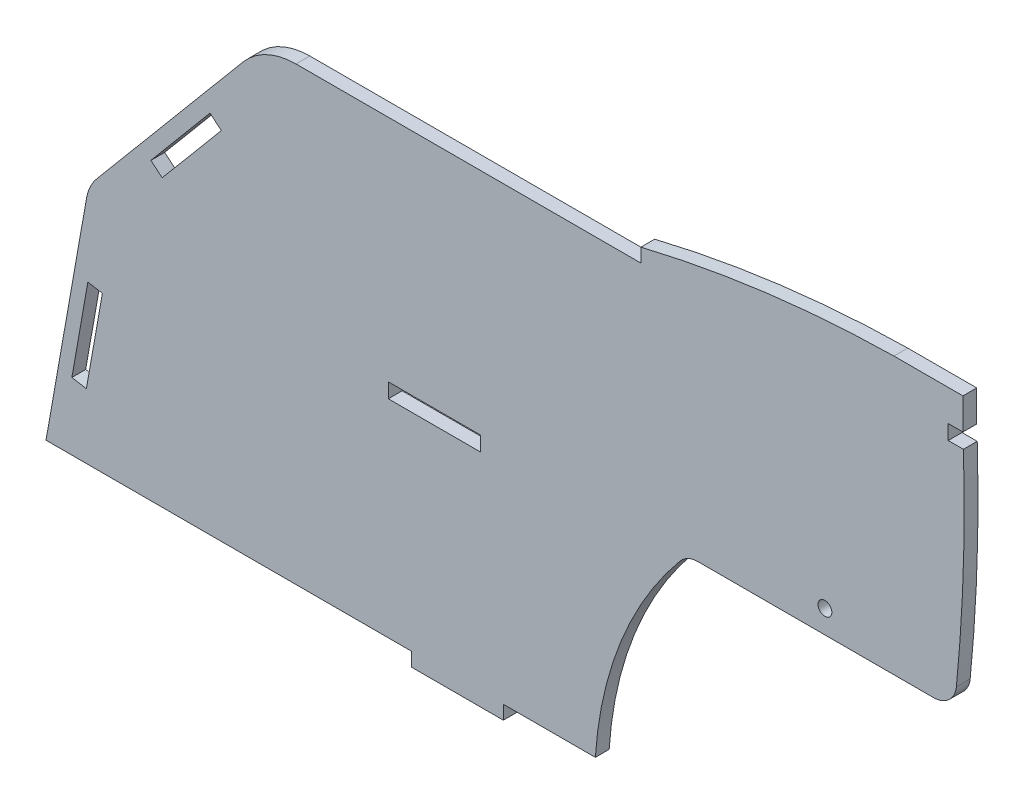
SolidWorks part; units mm, degrees
material "Acrylic (Medium-high impact)"
ref_plane "Front Plane" through (0, 0, 0) normal (0, 0, 1) x (1, 0, 0)
ref_plane "Top Plane" through (0, 0, 0) normal (0, 1, 0) x (1, 0, 0)
ref_plane "Right Plane" through (0, 0, 0) normal (1, 0, 0) x (0, 0, -1)
sketch "Sketch1" plane through (0, 0, 0) normal (0, 0, 1) x (1, 0, 0)
  line L0 (-45.0693, 73) -> (29.8996, 73)
  line L6 (93.5002, 23) -> (42.2917, 23)
  line L13 (-25, 23.2) -> (-5, 23.2)
  line L14 (-25, 23.2) -> (-25, 20)
  line L15 (-25, 20) -> (-5, 20)
  line L16 (-5, 23.2) -> (-5, 20)
  line L17 (-25, 23.2) -> (-5, 20) construction
  line L18 (-25, 20) -> (-5, 23.2) construction
  line L25 (-99.4082, -25) -> (-20, -25)
  line L26 (-20, -25) -> (-20, -27.9999)
  line L27 (-20, -27.9999) -> (0, -27.9999)
  line L28 (0, -27.9999) -> (0, -25)
  line L29 (0, -25) -> (20, -25)
  line L30 (0, 0) -> (-95, 0) construction
  line L31 (-88.4042, 29.6914) -> (-56.56, 67.6418)
  line L32 (-76.6118, 39.0778) -> (-74.1605, 37.0209)
  line L33 (-76.6118, 39.0778) -> (-63.7561, 54.3987)
  line L34 (-74.1605, 37.0209) -> (-61.3047, 52.3418)
  line L35 (-63.7561, 54.3987) -> (-61.3047, 52.3418)
  line L36 (-70.184, 46.7382) -> (-72.4821, 48.6666) construction
  line L38 (-90.5918, 25) -> (-99.4082, -25)
  line L39 (-93.7821, -10.369) -> (-90.3091, 9.3271)
  line L40 (-93.7821, -10.369) -> (-90.6307, -10.9247)
  line L41 (-90.3091, 9.3271) -> (-87.1577, 8.7715)
  line L42 (-90.6307, -10.9247) -> (-87.1577, 8.7715)
  line L43 (-92.0456, -0.5209) -> (-95, 0) construction
  line L44 (99.8996, 83) -> (84.8996, 83)
  line L45 (29.8996, 73) -> (29.8996, 76)
  line L46 (99.8996, 83) -> (99.8996, 76)
  arc A3 (20, -25) -> (38.4554, 21.2066) centre (99.8373, -30.0989) cw
  arc A5 (-45.0693, 73) -> (-56.56, 67.6418) centre (-45.0693, 58) ccw
  arc A7 (-88.4042, 29.6914) -> (-90.5918, 25) centre (-80.7437, 23.2635) ccw
  arc A13 (42.2917, 23) -> (38.4554, 21.2066) centre (42.2917, 18) ccw
  circle A14 centre (69.8996, 28) radius 1.5
  arc A17 (29.8996, 76) -> (84.8996, 83) centre (88.7685, -166.9701) cw
  arc A20 (98.4759, 27.5072) -> (99.8996, 76) centre (-249.8203, 62.0006) ccw
  arc A21 (98.4759, 27.5072) -> (93.5002, 23) centre (93.5002, 28) cw
  point P1 (0, 0)
  point P11 (-15, 21.6)
  point P33 (-95, 0)
  point P38 (-90.1265, 27.6388)
  point P45 (40, 23)
  point P52 (98, 23)
  dimension "D7" = 7
  dimension "D3" = 15
  dimension "D9" = 98
  dimension "D10" = 58
  dimension "D12" = 80
  dimension "D2" = 25
  dimension "D11" = 10
  dimension "D8" = 10
  dimension "D20" = 15
  dimension "D21" = 70
  dimension "D22" = 5
  dimension "D23" = 3
  dimension "D29" = 250
  dimension "D27" = 145
  dimension "D30" = 350
  dimension "D31" = 78
  dimension "D32" = 30
  dimension "D33" = 5
  dimension "D4" = 20
  dimension "D5" = 3.2
  dimension "D6" = 45
  dimension "D13" = 20
  dimension "D14" = 130
  dimension "D15" = 3
  dimension "D16" = 3
  dimension "100" = 95
  dimension "D17" = 280
  dimension "D18" = 15
  dimension "D19" = 20
  dimension "D24" = 48
  dimension "D25" = 2.9999
  dimension "D26" = 5
  dimension "D28" = 3
extrude "Boss-Extrude1" add sketch "Sketch1" along normal blind 3
sketch "Sketch2" plane through (0, 0, 3) normal (0, 0, 1) x (1, 0, 0)
  line L1 (96.7019, 76.2) -> (100.2019, 76.2)
  line L2 (96.7019, 76.2) -> (96.7019, 73)
  line L3 (96.7019, 73) -> (100.2019, 73)
  line L4 (100.2019, 76.2) -> (100.2019, 73)
  line L5 (96.7019, 76.2) -> (100.2019, 73) construction
  line L6 (96.7019, 73) -> (100.2019, 76.2) construction
  line L10 (29.8996, 73) -> (-45.0693, 73) construction
  arc A5 (98.4759, 27.5072) -> (99.8996, 76) centre (-249.8203, 62.0006) ccw construction
  point P0 (98.4519, 74.6)
  point P5 (0, 0)
  point P6 (0, 0)
  point P11 (0, 0)
  dimension "D1" = 3.2
  dimension "D2" = 3.5
  dimension "D3" = 1.5
extrude "Cut-Extrude1" cut sketch "Sketch2" against normal blind 10
